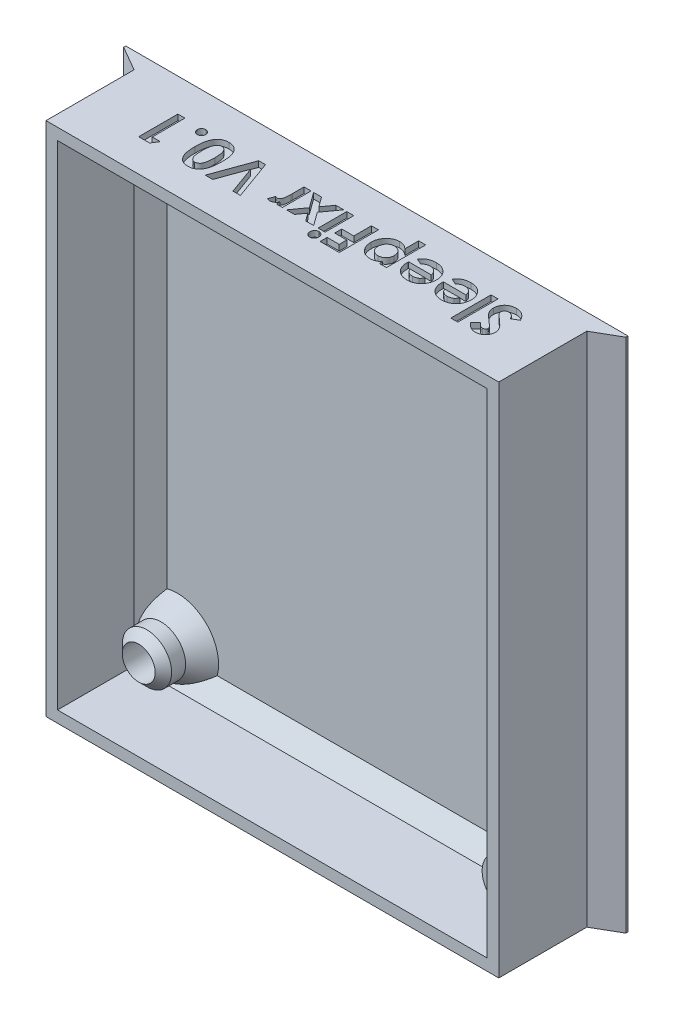
SolidWorks part; units mm, degrees
ref_plane "Front Plane" through (0, 0, 0) normal (0, 0, 1) x (1, 0, 0)
ref_plane "Top Plane" through (0, 0, 0) normal (0, 1, 0) x (1, 0, 0)
ref_plane "Right Plane" through (0, 0, 0) normal (1, 0, 0) x (0, 0, -1)
sketch "Sketch1" plane through (0, 0, 0) normal (0, 0, 1) x (1, 0, 0)
  line L0 (-27.5, 31.35) -> (27.5, -31.35) construction
  line L1 (-27.5, 31.35) -> (27.5, 31.35)
  line L2 (-27.5, 31.35) -> (-27.5, -31.35)
  line L3 (-27.5, -31.35) -> (27.5, -31.35)
  line L4 (27.5, 31.35) -> (27.5, -31.35)
  line L5 (-27.5, -31.35) -> (27.5, 31.35) construction
  point P4 (0, 0)
  dimension "D1" = 55
  dimension "D2" = 62.7
extrude "Boss-Extrude1" add sketch "Sketch1" along normal blind 12.7
shell "Shell1" thickness 1.4 removed face at (0, 0, 12.7)
sketch "Sketch2" plane through (0, 0, 1.4) normal (0, 0, 1) x (1, 0, 0)
  line L0 (24.4065, 26.6523) -> (21.3585, 26.6523) construction
  line L1 (22.8825, 28.1763) -> (22.8825, 25.1283) construction
  circle A0 centre (22.8825, 26.6523) radius 3
  circle A1 centre (22.8825, -26.6878) radius 2
  circle A2 centre (22.8825, 26.6523) radius 2
  circle A3 centre (22.8825, 26.6523) radius 1.524 construction
  circle A4 centre (22.8825, -26.6878) radius 3
  circle A5 centre (-22.8376, -26.6878) radius 3
  circle A6 centre (-22.8376, -26.6878) radius 2
  dimension "D1" = 6
  dimension "D2" = 26.6523
  dimension "D3" = 22.8825
  dimension "D4" = 4
  dimension "D5" = 2
  dimension "D6" = 53.3401
  dimension "D8" = 45.7201
  dimension "D7" = 2
extrude "Boss-Extrude2" add sketch "Sketch2" along normal blind 5.7
sketch "Sketch3" plane through (0, 0, 0) normal (0, 0, -1) x (-1, 0, 0)
  line L0 (27.5, -31.35) -> (-27.5, -31.35) construction
  line L1 (-27.5, 31.35) -> (-30.5, 31.35)
  line L2 (-27.5, 31.35) -> (-27.5, -31.35)
  line L3 (-27.5, -31.35) -> (-30.5, -31.35)
  line L4 (-30.5, 31.35) -> (-30.5, -31.35)
  line L5 (0, 31.35) -> (0, -31.35) construction
  line L6 (-27.5, 31.35) -> (27.5, 31.35) construction
  dimension "D1" = 3
extrude "Boss-Extrude3" add sketch "Sketch3" against normal blind 2
chamfer "Chamfer1" distance 3 angle 30 1 edges at (30.5, 0, 2) first distance on face at (29, 0, 2)
ref_plane "Plane1" through (0, 0, 0) normal (-1, 0, 0) x (0, 0, 1)
mirror "Mirror1" about plane through (0, 0, 0) normal (-1, 0, 0) of "Chamfer1", "Boss-Extrude3"
sketch "Sketch4" plane through (0, 31.35, 0) normal (0, 1, 0) x (1, 0, 0)
  line L0 (-27.5, -4) -> (27.5, -4) construction
  text T0 "<b>SleepFixr V0.1</b>" font "Century Gothic" height in points 18
  dimension "D1" = 4
  dimension "D2" = 55
  dimension "D3" = 27.5
extrude "Cut-Extrude1" cut sketch "Sketch4" against normal blind 0.7
chamfer "Chamfer2" distance 2 angle 45 8 edges at (-19.8376, -26.6878, 7.1) (0, 29.95, 1.4) (26.1, 0, 1.4) (0, -29.95, 1.4) (-26.1, 0, 1.4) (25.8825, 26.6523, 1.4) (25.8825, -26.6878, 1.4) (-19.8376, -26.6878, 1.4)
